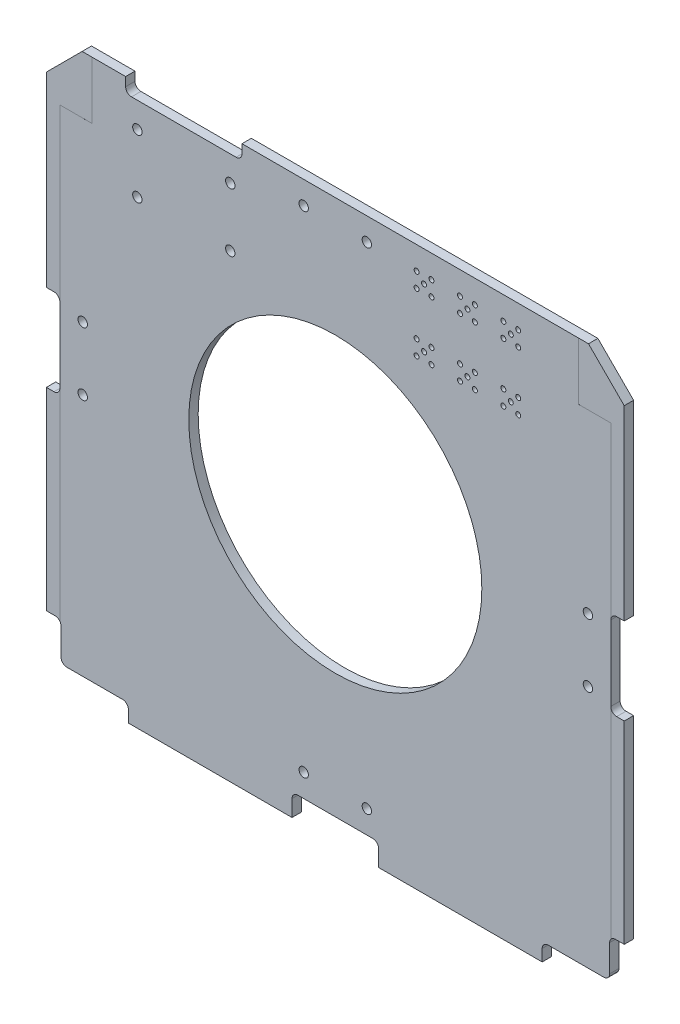
SolidWorks part; units mm, degrees
material "Oshpark board"
ref_plane "Front Plane" through (0, 0, 0) normal (0, 0, 1) x (1, 0, 0)
ref_plane "Top Plane" through (0, 0, 0) normal (0, 1, 0) x (1, 0, 0)
ref_plane "Right Plane" through (0, 0, 0) normal (1, 0, 0) x (0, 0, -1)
ref_plane "Plane4" through (0, 0, -0.0125) normal (0, 0, -1) x (-1, 0, 0)
sketch "Sketch1" plane through (0, 0, -0.0125) normal (0, 0, -1) x (-1, 0, 0)
  line L0 (35.3, -50) -> (35.3, -48)
  line L1 (36.3, -47) -> (45.8, -47)
  line L2 (46.8, -46) -> (46.8, -41.4)
  line L3 (47.8, -40.4) -> (49.3, -40.4)
  line L4 (49.3, -40.4) -> (49.3, 39.2)
  line L5 (49.3, 39.2) -> (43.2, 45.3)
  line L6 (43.2, 45.3) -> (35.5, 45.3)
  line L7 (35.5, 45.3) -> (35.5, 43.8) construction
  line L8 (34.5, 42.8) -> (4.5, 42.8) construction
  line L9 (3.5, 43.8) -> (3.5, 45.3) construction
  line L10 (3.5, 45.3) -> (-43.2, 45.3)
  line L11 (-43.2, 45.3) -> (-49.3, 39.2)
  line L12 (-49.3, 39.2) -> (-49.3, -40.4)
  line L13 (-49.3, -40.4) -> (-47.8, -40.4)
  line L14 (-46.8, -41.4) -> (-46.8, -46)
  line L15 (-45.8, -47) -> (-36.3, -47)
  line L16 (-35.3, -48) -> (-35.3, -50)
  line L17 (-35.3, -50) -> (35.3, -50)
  line L18 (0, -50) -> (0, 45.3) construction
  line L19 (19.5, 42.8) -> (19.5, 25.5258) construction
  line L20 (-13.87, 41.37) -> (-16.41, 38.83) construction
  line L21 (-21.27, 41.37) -> (-23.81, 38.83) construction
  line L22 (-28.67, 41.37) -> (-31.21, 38.83) construction
  line L23 (35.5, 45.3) -> (3.5, 45.3)
  arc A0 (35.3, -48) -> (36.3, -47) centre (36.3, -48) cw
  arc A1 (45.8, -47) -> (46.8, -46) centre (45.8, -46) ccw
  arc A2 (46.8, -41.4) -> (47.8, -40.4) centre (47.8, -41.4) cw
  arc A3 (35.5, 43.8) -> (34.5, 42.8) centre (34.5, 43.8) cw construction
  arc A4 (4.5, 42.8) -> (3.5, 43.8) centre (4.5, 43.8) cw construction
  arc A5 (-47.8, -40.4) -> (-46.8, -41.4) centre (-47.8, -41.4) cw
  arc A6 (-46.8, -46) -> (-45.8, -47) centre (-45.8, -46) ccw
  arc A7 (-36.3, -47) -> (-35.3, -48) centre (-36.3, -48) cw
  circle A8 centre (-21.27, 41.37) radius 0.425
  circle A9 centre (-23.81, 41.37) radius 0.425
  circle A10 centre (-22.54, 40.1) radius 0.425
  circle A11 centre (-13.87, 41.37) radius 0.425
  circle A12 centre (-23.81, 38.83) radius 0.425
  circle A13 centre (-16.41, 41.37) radius 0.425
  circle A14 centre (-15.14, 40.1) radius 0.425
  circle A15 centre (-21.27, 38.83) radius 0.425
  circle A16 centre (-28.67, 41.37) radius 0.425
  circle A17 centre (-31.21, 41.37) radius 0.425
  circle A18 centre (-16.41, 38.83) radius 0.425
  circle A19 centre (-29.94, 40.1) radius 0.425
  circle A20 centre (-31.21, 38.83) radius 0.425
  circle A21 centre (-28.67, 38.83) radius 0.425
  circle A22 centre (33.775, 38.54) radius 0.8 construction
  circle A23 centre (5.225, 38.54) radius 0.8 construction
  circle A24 centre (-13.87, 38.83) radius 0.425
  point P35 (-15.14, 40.1)
  dimension "D7" = 2.5
  dimension "D8" = 1.6
  dimension "D9" = 14.275
  dimension "D10" = 4.26
  dimension "D11" = 1
  dimension "D12" = 1
  dimension "D13" = 1
  dimension "D14" = 1
  dimension "D15" = 1
  dimension "D16" = 1
  dimension "D17" = 1
  dimension "D18" = 1
  dimension "D26" = 0.85
  dimension "D1" = 98.6
  dimension "D2" = 95.3
  dimension "D3" = 14
  dimension "D4" = 9.6
  dimension "D5" = 2.5
  dimension "D6" = 3
  dimension "D19" = 14
  dimension "D20" = 2.5
  dimension "D21" = 6.1
  dimension "D22" = 6.1
  dimension "D23" = 32
  dimension "D24" = 2.54
  dimension "D25" = 2.54
  dimension "D28" = 7.4
  dimension "D29" = 3.93
  dimension "D30" = 35.43
  dimension "D31" = 45
  dimension "D32" = 45
  dimension "D33" = 29.8
  dimension "D34" = 50
  dimension "D27" = 3
extrude "Boss-Extrude1" add sketch "Sketch1" against normal blind 1.6
sketch "thermalContacts_lower" plane through (0, 0, -0.0125) normal (0, 0, -1) x (-1, 0, 0)
  line L0 (47, 35.5) -> (47, -41.5) construction
  line L1 (41.5, 35.5) -> (41.5, 41.5) construction
  line L2 (41.5, 35.5) -> (47, 35.5) construction
  line L3 (47, 35.5) -> (47, -41.5)
  line L4 (41.5, 35.5) -> (41.5, 41.5)
  line L5 (41.5, 35.5) -> (47, 35.5)
  line L6 (-47, 35.5) -> (-47, -41.5) construction
  line L7 (-41.5, 35.5) -> (-47, 35.5) construction
  line L8 (-41.5, 35.5) -> (-41.5, 41.5) construction
  line L9 (-47, 35.5) -> (-47, -41.5)
  line L10 (-41.5, 35.5) -> (-47, 35.5)
  line L11 (-41.5, 35.5) -> (-41.5, 41.5)
  line L12 (-41.5, 41.5) -> (-41.5, 47) construction
  line L13 (-41.5, 41.5) -> (-49.5, 41.5) construction
  line L14 (-41.5, 41.5) -> (-41.5, 47)
  line L15 (-41.5, 41.5) -> (-49.5, 41.5) construction
  line L16 (41.5, 41.5) -> (41.5, 47) construction
  line L17 (41.5, 41.5) -> (49.5, 41.5) construction
  line L18 (41.5, 41.5) -> (41.5, 47)
  line L19 (41.5, 41.5) -> (49.5, 41.5) construction
  line L20 (47, -41.5) -> (59.8273, -41.5)
  line L21 (59.8273, -41.5) -> (59.8273, 47)
  line L22 (-56.1922, 47) -> (-41.5, 47)
  line L23 (41.5, 47) -> (59.8273, 47)
  line L24 (-56.1922, 47) -> (-56.1922, -41.5)
  line L25 (-47, -41.5) -> (-56.1922, -41.5)
sketch "thermalContacts_upper" plane through (0, 0, 1.5875) normal (0, 0, 1) x (1, 0, 0)
  line L3 (-47, 35.5) -> (-47, -41.5)
  line L4 (-41.5, 35.5) -> (-41.5, 41.5)
  line L5 (-41.5, 35.5) -> (-47, 35.5)
  line L9 (47, 35.5) -> (47, -41.5)
  line L10 (41.5, 35.5) -> (47, 35.5)
  line L11 (41.5, 35.5) -> (41.5, 41.5)
  line L14 (41.5, 41.5) -> (41.5, 47)
  line L15 (41.5, 41.5) -> (49.5, 41.5) construction
  line L18 (-41.5, 41.5) -> (-41.5, 47)
  line L19 (-41.5, 41.5) -> (-49.5, 41.5) construction
  line L20 (47, -41.5) -> (59.8273, -41.5)
  line L21 (59.8273, -41.5) -> (59.8273, 47)
  line L22 (59.8273, 47) -> (41.5, 47)
  line L23 (-41.5, 47) -> (-56.1922, 47)
  line L24 (-56.1922, 47) -> (-56.1922, -41.5)
  line L25 (-56.1922, -41.5) -> (-47, -41.5)
pattern_linear "LPattern2" count 2 spacing 10 along (0, -1, 0) of face at (14.295, 41.37, 1.5875) of face at (14.295, 38.83, 1.5875) of face at (15.565, 40.1, 1.5875) of face at (16.835, 38.83, 1.5875) of face at (21.695, 41.37, 1.5875) of face at (21.695, 38.83, 1.5875) of face at (22.965, 40.1, 1.5875) of face at (24.235, 38.83, 1.5875) of face at (24.235, 41.37, 1.5875) of face at (16.835, 41.37, 1.5875) of face at (29.095, 41.37, 1.5875) of face at (29.095, 38.83, 1.5875) of face at (30.365, 40.1, 1.5875) of face at (31.635, 38.83, 1.5875) of face at (31.635, 41.37, 1.5875)
extrude "slotFootprints_REF" cut sketch "thermalContacts_lower" against normal blind 0.0001
extrude "slotFootprints" cut sketch "thermalContacts_upper" against normal blind 0.0001
sketch "Sketch2" plane through (0, 0, 1.5875) normal (0, 0, 1) x (1, 0, 0)
  line L1 (-41.5, 45.3) -> (41.5, 45.3) construction
  line L2 (-49.3, -40.4) -> (-49.3, 39.2) construction
  line L3 (-35.775, 45.3) -> (-35.775, 43.8)
  line L4 (-41.5, 45.3) -> (41.5, 45.3) construction
  line L5 (-34.775, 42.8) -> (-16.925, 42.8)
  line L6 (-15.925, 43.8) -> (-15.925, 45.3)
  line L7 (-15.925, 45.3) -> (-35.775, 45.3)
  arc A1 (-16.925, 42.8) -> (-15.925, 43.8) centre (-16.925, 43.8) ccw
  arc A2 (-35.775, 43.8) -> (-34.775, 42.8) centre (-34.775, 43.8) ccw
  circle A3 centre (-33.775, 38.4723) radius 0.8
  circle A4 centre (-17.925, 38.4723) radius 0.8
  circle A5 centre (-17.925, 28.4723) radius 0.8
  circle A6 centre (-33.775, 28.4723) radius 0.8
  dimension "D2" = 1.6
  dimension "D5" = 1
  dimension "D1" = 15.85
  dimension "D3" = 6.8277
  dimension "D4" = 15.525
  dimension "D6" = 2
  dimension "D7" = 2
  dimension "D8" = 2.5
  dimension "D10" = 10
  dimension "D9" = 2
extrude "20pin_mounts" cut sketch "Sketch2" against normal through all
sketch "Sketch3" plane through (0, 0, -0.0125) normal (0, 0, -1) x (-1, 0, 0)
  line L0 (-49.3, -40.4) -> (-49.3, 39.2) construction
  line L1 (5.39, 41.4) -> (-5.38, 41.4) construction
  line L2 (43.1, -5.39) -> (43.1, 5.38) construction
  line L3 (15.925, 45.3) -> (-41.5, 45.3) construction
  line L4 (5.39, -42.3032) -> (-5.38, -42.3032) construction
  line L5 (-43.1, -5.39) -> (-43.1, 5.38) construction
  line L6 (41.5, 45.3) -> (35.775, 45.3) construction
  line L7 (43.1, -0.005) -> (-43.1, -0.005) construction
  line L8 (0.005, -42.3032) -> (0.005, 41.4) construction
  line L9 (49.3, -40.4) -> (49.3, 39.2) construction
  line L10 (-35.3, -50) -> (35.3, -50) construction
  line L11 (-43.1, -0.005) -> (-49.3, -0.005) construction
  line L12 (43.1, -0.005) -> (49.3, -0.005) construction
  line L13 (49.3, -40.4) -> (49.3, 39.2) construction
  line L14 (-49.3, 7.38) -> (-48, 7.38)
  line L15 (-47, 6.38) -> (-47, -6.39)
  line L16 (-48, -7.39) -> (-49.3, -7.39)
  line L17 (-49.3, -7.39) -> (-49.3, 7.38)
  line L18 (-49.3, -40.4) -> (-49.3, 39.2) construction
  line L19 (-47, 35.5) -> (-47, -40.8) construction
  line L20 (47, -40.8) -> (47, 35.5) construction
  line L21 (48, 7.38) -> (49.3, 7.38)
  line L22 (47, 6.38) -> (47, -6.39)
  line L23 (48, -7.39) -> (49.3, -7.39)
  line L24 (49.3, 7.38) -> (49.3, -7.39)
  line L26 (-6.38, -46.2032) -> (6.39, -46.2032)
  line L27 (-7.38, -47.2032) -> (-7.38, -50)
  line L28 (-7.38, -50) -> (7.39, -50)
  line L29 (7.39, -47.2032) -> (7.39, -50)
  arc A0 (-47, -6.39) -> (-48, -7.39) centre (-48, -6.39) cw
  arc A1 (-48, 7.38) -> (-47, 6.38) centre (-48, 6.38) cw
  circle A2 centre (5.39, 41.4) radius 0.8
  circle A3 centre (-5.38, 41.4) radius 0.8
  arc A4 (47, -6.39) -> (48, -7.39) centre (48, -6.39) ccw
  arc A5 (48, 7.38) -> (47, 6.38) centre (48, 6.38) ccw
  arc A6 (-6.38, -46.2032) -> (-7.38, -47.2032) centre (-6.38, -47.2032) ccw
  circle A7 centre (43.1, 5.38) radius 0.8
  circle A8 centre (43.1, -5.39) radius 0.8
  circle A9 centre (5.39, -42.3032) radius 0.8
  circle A10 centre (-5.38, -42.3032) radius 0.8
  circle A11 centre (-43.1, -5.39) radius 0.8
  circle A12 centre (-43.1, 5.38) radius 0.8
  arc A13 (6.39, -46.2032) -> (7.39, -47.2032) centre (6.39, -47.2032) cw
  point P16 (-47, -0.005)
  point P51 (47, -0.005)
  point P63 (0.005, -46.2032)
  dimension "D1" = 1.6
  dimension "D5" = 39.92
  dimension "D6" = 6.2
  dimension "D9" = 1
  dimension "D11" = 1
  dimension "D14" = 1
  dimension "D2" = 10.77
  dimension "D3" = 43.92
  dimension "D4" = 3.9
  dimension "D7" = 7.6968
  dimension "D8" = 2
  dimension "D10" = 2
  dimension "D12" = 3.9
  dimension "D13" = 2
extrude "12pin_mounts" cut sketch "Sketch3" against normal blind 10
sketch "Sketch4" plane through (0, 0, -0.0125) normal (0, 0, -1) x (-1, 0, 0)
  circle A0 centre (0, 0) radius 25
  dimension "D1" = 50
extrude "Cut-Extrude1" cut sketch "Sketch4" against normal through all
